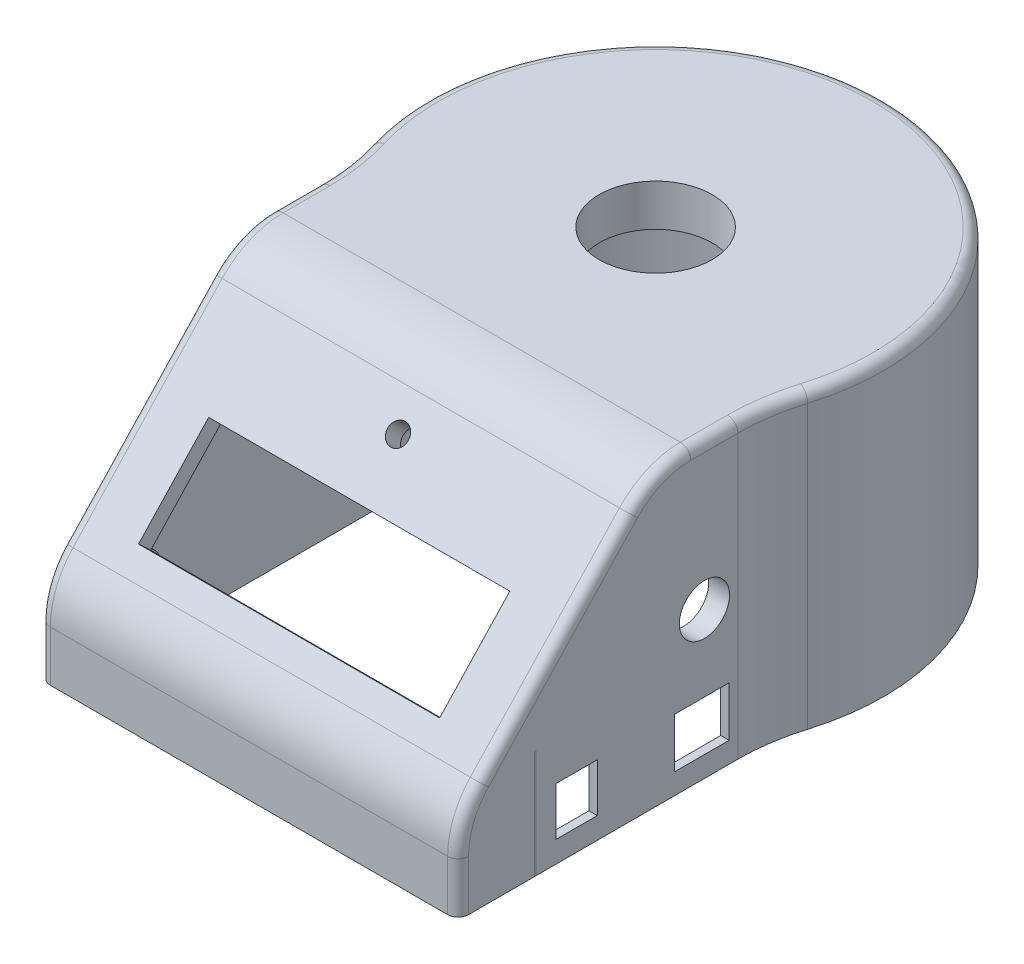
SolidWorks part; units mm, degrees
ref_plane "Front Plane" through (0, 0, 0) normal (0, 0, 1) x (1, 0, 0)
ref_plane "Top Plane" through (0, 0, 0) normal (0, 1, 0) x (1, 0, 0)
ref_plane "Right Plane" through (0, 0, 0) normal (1, 0, 0) x (0, 0, -1)
sketch "Sketch1" plane through (0, 0, 0) normal (0, 1, 0) x (1, 0, 0)
  circle A0 centre (0, 0) radius 54.5
  circle A1 centre (0, 0) radius 50
extrude "Boss-Extrude1" add sketch "Sketch1" along normal blind 60
sketch "Sketch2" plane through (0, 60, 0) normal (0, 1, 0) x (1, 0, 0)
  circle A0 centre (0, 0) radius 54.5
  circle A1 centre (0, 0) radius 13.5
extrude "Boss-Extrude2" add sketch "Sketch2" along normal blind 10
sketch "Sketch3" plane through (0, 0, 0) normal (0, -1, 0) x (1, 0, 0)
  line L0 (-50, 0) -> (-50, 97.2352)
  line L5 (-50, 97.2352) -> (50, 97.2352)
  line L6 (50, 97.2352) -> (50, 0)
  circle A0 centre (0, 0) radius 50 construction
  circle A1 centre (0, 0) radius 50 construction
  arc A3 (-50, 0) -> (50, 0) centre (0, 0) cw
extrude "Boss-Extrude4" add sketch "Sketch3" against normal blind 70 contours L6 A3 L0 L5
sketch "Sketch4" plane through (50, 0, 0) normal (1, 0, 0) x (0, 0, -1)
  line L3 (-97.2352, 70) -> (-97.2352, 20)
  line L8 (-97.2352, 70) -> (-97.2352, 0) construction
  line L9 (-97.2352, 20) -> (-97.2352, 70)
  line L10 (-97.2352, 70) -> (-50.2352, 70)
  line L11 (-97.2352, 70) -> (-21.6852, 70) construction
  line L12 (-50.2352, 70) -> (-97.2352, 20)
  dimension "D1" = 50
  dimension "D2" = 47
extrude "Cut-Extrude3" cut sketch "Sketch4" against normal blind 100 contours L10 L12 L3
shell "Shell1" thickness 5 removed face at (0, 0, 40.4139)
sketch "Sketch5" plane through (0, 0, 0) normal (0, -1, 0) x (1, 0, 0)
  line L0 (-45, 31.6228) -> (-45, 21.7945)
  line L1 (45, 31.6228) -> (45, 21.7945)
  circle A0 centre (0, 0) radius 50 construction
  arc A1 (-45, 21.7945) -> (45, 21.7945) centre (0, 0) cw
  arc A2 (-45, 31.6228) -> (45, 31.6228) centre (0, 0) cw
extrude "Cut-Extrude4" cut sketch "Sketch5" against normal blind 60
sketch "Sketch11" plane through (0, 0, 0) normal (0, -1, 0) x (1, 0, 0)
  line L0 (-50, 21.6852) -> (-50, 97.2352)
  line L1 (-50, 97.2352) -> (50, 97.2352)
  line L2 (50, 97.2352) -> (50, 21.6852)
  arc A0 (-50, 21.6852) -> (50, 21.6852) centre (0, 0) ccw
sketch "Sketch12" plane through (0, 57.9067, 61.6029) normal (0, 0.6849, 0.7286) x (1, 0, 0)
  line L0 (50, 16.5974) -> (50, -52.0248) construction
  line L1 (-36, -13.5248) -> (36, -13.5248)
  line L2 (-36, -13.5248) -> (-36, -38.0248)
  line L3 (-36, -38.0248) -> (36, -38.0248)
  line L4 (36, -13.5248) -> (36, -38.0248)
  line L5 (-50, 16.5974) -> (-50, -52.0248) construction
  line L6 (-50, -52.0248) -> (50, -52.0248) construction
  dimension "D1" = 24.5
  dimension "D2" = 72
  dimension "D3" = 14
  dimension "D4" = 14
  dimension "D5" = 14
extrude "Cut-Extrude5" cut sketch "Sketch12" against normal blind 4
sketch "Sketch13" plane through (0, 54.4822, 57.9597) normal (0, -0.6849, -0.7286) x (-1, 0, 0)
  line L1 (-40, -7.0248) -> (40, -7.0248)
  line L2 (-40, -7.0248) -> (-40, -43.0248)
  line L3 (-40, -43.0248) -> (40, -43.0248)
  line L4 (40, -7.0248) -> (40, -43.0248)
  line L6 (-36, -13.5248) -> (36, -13.5248) construction
  line L7 (36, -38.0248) -> (-36, -38.0248) construction
  line L8 (-36, -38.0248) -> (-36, -13.5248) construction
  dimension "D1" = 80
  dimension "D2" = 36
  dimension "D3" = 6.5
  dimension "D4" = 5
  dimension "D5" = 4
extrude "Cut-Extrude6" cut sketch "Sketch13" against normal up to vertex (1 mm away) up to point (36, 45.3125, 67.9516)
sketch "Sketch15" plane through (0, 57.9067, 61.6029) normal (0, 0.6849, 0.7286) x (1, 0, 0)
  line L0 (-40, -7.0248) -> (40, -7.0248) construction
  line L1 (-40, -43.0248) -> (-40, -7.0248) construction
  line L2 (40, -43.0248) -> (-40, -43.0248) construction
  line L3 (40, -7.0248) -> (40, -43.0248) construction
  circle A0 centre (-37.5, -9.5248) radius 2.75
  circle A1 centre (37.5, -9.5248) radius 2.75
  circle A2 centre (-37.5, -40.5248) radius 2.75
  circle A3 centre (37.5, -40.5248) radius 2.75
  dimension "D1" = 2.5
  dimension "D2" = 2.5
  dimension "D3" = 2.5
  dimension "D4" = 2.5
  dimension "D5" = 2.5
  dimension "D6" = 2.5
  dimension "D7" = 2.5
  dimension "D8" = 2.5
extrude "Boss-Extrude5" add sketch "Sketch15" against normal blind 7
hole_wizard "M3 Clearance Hole1" positions "Sketch16" profile "Sketch17" hole size "M3" standard "ANSI Metric"
sketch "Sketch16" plane through (0, 53.1123, 56.5025) normal (0, -0.6849, -0.7286) x (-1, 0, 0)
  point P0 (-37.5, -9.5248)
  point P3 (37.5, -9.5248)
  point P6 (37.5, -40.5248)
  point P9 (-37.5, -40.5248)
sketch "Sketch17" plane through (37.5, 46.1723, 63.0261) normal (1, 0, 0) x (0, 0.7286, -0.6849)
  line L0 (0, 0) -> (0, 6.0215)
  line L1 (0, 6.0215) -> (1.7, 5)
  line L2 (1.7, 5) -> (1.7, 0.025)
  line L3 (1.7, 0.025) -> (1.725, 0)
  line L5 (1.725, 0) -> (0, 0)
  line L6 (-1.7, 0.025) -> (-1.725, 0) construction
  line L10 (0, 6.0215) -> (-1.7, 5) construction
  line L11 (0, -6.35) -> (0, 107.95) construction
  dimension "Hole Dia." = 3.4
  dimension "Hole Depth" = 5
  dimension "Near C'Sink Dia." = 3.45
  dimension "Near C'Sink Angle" = 90
  dimension "Drill Angle" = 118
sketch "Sketch19" plane through (0, 0, 0) normal (0, -1, 0) x (-1, 0, 0)
  line L0 (50, -97.2352) -> (-50, -97.2352) construction
  line L1 (50, -21.6852) -> (50, -97.2352) construction
  line L2 (-50, -97.2352) -> (-50, -21.6852) construction
  circle A0 centre (40, -87.2352) radius 5
  circle A1 centre (-40, -87.2352) radius 5
  dimension "D1" = 10
  dimension "D2" = 10
  dimension "D3" = 10
  dimension "D4" = 10
extrude "Boss-Extrude6" add sketch "Sketch19" against normal blind 15 separate body
sketch "Sketch20" plane through (0, 0, 0) normal (0, -1, 0) x (1, 0, 0)
  line L0 (-40, 92.2352) -> (-45, 92.2352)
  line L1 (-45, 92.2352) -> (45, 92.2352) construction
  line L2 (-45, 92.2352) -> (-45, 87.2352)
  line L3 (-45, 21.7945) -> (-45, 92.2352) construction
  line L4 (45, 92.2352) -> (45, 21.7945) construction
  line L5 (40, 92.2352) -> (45, 92.2352)
  line L6 (-45, 92.2352) -> (45, 92.2352) construction
  line L7 (45, 92.2352) -> (45, 87.2352)
  circle A0 centre (-40, 87.2352) radius 5 construction
  arc A1 (-45, 87.2352) -> (-40, 92.2352) centre (-40, 87.2352) cw
  arc A2 (40, 92.2352) -> (45, 87.2352) centre (40, 87.2352) cw
  circle A3 centre (40, 87.2352) radius 5 construction
extrude "Boss-Extrude7" add sketch "Sketch20" against normal blind 15
sketch "Sketch21" plane through (0, 0, 0) normal (0, -1, 0) x (1, 0, 0)
  line L0 (50, 97.2352) -> (50, 21.6852) construction
  circle A0 centre (47, 1.6852) radius 5
  circle A1 centre (-47, 1.6852) radius 5
  dimension "D1" = 20
  dimension "D2" = 3
  dimension "D3" = 20
  dimension "D4" = 3
extrude "Boss-Extrude8" add sketch "Sketch21" against normal blind 15
hole_wizard "Tap Drill for M4x0.7 Tap1" positions "3DSketch1" profile "Sketch23" hole size "M4x0.7" standard "ANSI Metric" end condition up to next
sketch3d "3DSketch1"
  line L0 (-47, 15, 1.6852) -> (-47, 0, 1.6852) construction
  line L1 (47, 15, 1.6852) -> (47, 0, 1.6852) construction
  line L2 (40, 15, 87.2352) -> (40, 0, 87.2352) construction
  line L3 (-40, 15, 87.2352) -> (-40, 0, 87.2352) construction
  point P0 (-47, 0, 1.6852)
  point P4 (47, 0, 1.6852)
  point P8 (40, 0, 87.2352)
  point P12 (-40, 0, 87.2352)
sketch "Sketch23" plane through (-47, 0, 1.6852) normal (1, 0, 0) x (0, 0, -1)
  line L0 (0, 0) -> (0, 15)
  line L1 (0, 15) -> (1.65, 15)
  line L2 (1.65, 15) -> (1.65, 0.025)
  line L3 (1.65, 0.025) -> (1.675, 0)
  line L5 (1.675, 0) -> (0, 0)
  line L6 (-1.65, 0.025) -> (-1.675, 0) construction
  line L11 (0, -6.35) -> (0, 107.95) construction
  dimension "Thru Hole Dia." = 3.3
  dimension "Thru Hole Depth" = 15
  dimension "Near C'Sink Dia." = 3.35
  dimension "Near C'Sink Angle" = 90
sketch "Sketch24" plane through (50, 0, 0) normal (1, 0, 0) x (0, 0, -1)
  line L1 (-21.6852, 0) -> (-78.9852, 0)
  line L2 (-21.6852, 0) -> (-21.6852, 26)
  line L3 (-21.6852, 26) -> (-78.9852, 26)
  line L4 (-78.9852, 0) -> (-78.9852, 26)
  dimension "D1" = 26
  dimension "D2" = 57.3
extrude "Cut-Extrude7" cut sketch "Sketch24" against normal blind 5
sketch "Sketch25" plane through (50, 0, 50) normal (1, 0, 0) x (0, 0, 1)
  line L0 (-28.3148, -26) -> (28.9852, -26) construction
  line L1 (-28.6534, -26) -> (28.6466, -26)
  line L2 (-28.6534, -26) -> (-28.6534, 0)
  line L3 (-28.6534, 0) -> (28.6466, 0)
  line L4 (28.6466, -26) -> (28.6466, 0)
  line L5 (-17.5534, -4.96) -> (-4.5534, -4.96)
  line L6 (-17.5534, -4.96) -> (-17.5534, -16.86)
  line L7 (-17.5534, -16.86) -> (-4.5534, -16.86)
  line L8 (-4.5534, -4.96) -> (-4.5534, -16.86)
  line L9 (13.9466, -5.13) -> (23.8466, -5.13)
  line L10 (13.9466, -5.13) -> (13.9466, -16.69)
  line L11 (13.9466, -16.69) -> (23.8466, -16.69)
  line L12 (23.8466, -5.13) -> (23.8466, -16.69)
  dimension "D1" = 0
  dimension "D2" = 9.31
  dimension "D3" = 9.14
  dimension "D4" = 11.1
  dimension "D5" = 4.8
extrude "Boss-Extrude9" add sketch "Sketch25" against normal blind 2
sketch "Sketch26" plane through (50, 0, 0) normal (1, 0, 0) x (0, 0, -1)
  line L1 (-78.9852, 26) -> (-78.6466, 26)
  line L2 (-78.9852, 26) -> (-78.9852, 0)
  line L3 (-78.9852, 0) -> (-78.6466, 0)
  line L4 (-78.6466, 26) -> (-78.6466, 0)
extrude "Boss-Extrude10" add sketch "Sketch26" against normal blind 2 separate body
fillet "Fillet1" radius 50 2 edges at (50, 35, 21.6852) (-50, 35, 21.6852)
fillet "Fillet2" radius 20 1 edges at (0, 20, 97.2352)
fillet "Fillet3" radius 20 1 edges at (0, 70, 50.2352)
fillet "Fillet4" radius 2.5 13 edges at (-50, 6.0378, 97.2352) (-50, 19.4428, 95.8289) (50, 6.0378, 97.2352) (50, 19.4428, 95.8289) (50, 44.736, 73.9833) (-50, 44.736, 73.9833) (-50, 68.3571, 49.5247) (-50, 70, 35.961) (-50.5412, 70, 22.9989) (0, 70, -54.5) (50.5412, 70, 22.9989) (50, 70, 35.961) (50, 68.3571, 49.5247)
sketch "Sketch27" plane through (0, 54.4822, 57.9597) normal (0, -0.6849, -0.7286) x (-1, 0, 0)
  circle A0 centre (0, 0) radius 2.5
  point P0 (0, 0)
extrude "Cut-Extrude8" cut sketch "Sketch27" against normal up to next (5 mm away)
sketch "Sketch28" plane through (50, 0, 0) normal (1, 0, 0) x (0, 0, -1)
  line L0 (-21.6852, 0) -> (-97.2352, 0) construction
  line L1 (-30.3356, 0) -> (-30.3356, 67.5) construction
  point P0 (-38.3356, 35)
  point P3 (0, 0)
  dimension "D1" = 35
  dimension "D2" = 8
hole_wizard "Hole1" positions "3DSketch2" profile "Sketch30" legacy end condition up to next
sketch3d "3DSketch2"
  point P0 (50, 35, 38.3356)
sketch "Sketch30" plane through (50, 35, 38.3356) normal (0, 1, 0) x (0, 0, -1)
  line L0 (0, 0) -> (0, 5.001)
  line L1 (0, 5.001) -> (6, 5.001)
  line L2 (6, 5.001) -> (6, 0)
  line L3 (6, 0) -> (0, 0)
  line L4 (0, 110) -> (0, -10) construction
  dimension "Diameter" = 12
  dimension "Depth" = 5.001
